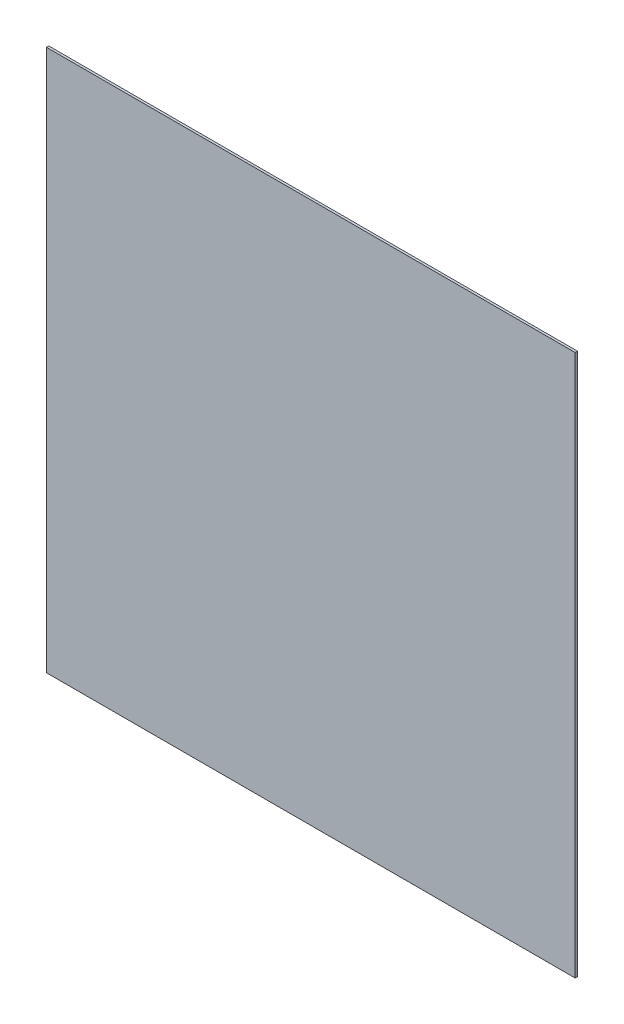
SolidWorks part; units mm, degrees
material "AISI 304"
ref_plane "Front Plane" through (0, 0, 0) normal (0, 0, 1) x (1, 0, 0)
ref_plane "Top Plane" through (0, 0, 0) normal (0, 1, 0) x (1, 0, 0)
ref_plane "Right Plane" through (0, 0, 0) normal (1, 0, 0) x (0, 0, -1)
sketch "Sketch1" plane through (0, 0, 0) normal (0, 0, 1) x (1, 0, 0)
  line L1 (-170.25, -174.5) -> (170.25, -174.5)
  line L2 (-170.25, -174.5) -> (-170.25, 174.5)
  line L3 (-170.25, 174.5) -> (170.25, 174.5)
  line L4 (170.25, -174.5) -> (170.25, 174.5)
  line L5 (-170.25, -174.5) -> (170.25, 174.5) construction
  line L6 (-170.25, 174.5) -> (170.25, -174.5) construction
  point P0 (0, 0)
  dimension "D1" = 340.5
  dimension "D2" = 349
base flange "Base-Flange1" sketch "Sketch1" thickness 1.5 reverse thickness direction no parameters "D1"=2
sketch "Bend-Lines1" [suppressed] plane through (0, 0, 0) normal (0, 1, 0) x (1, 0, 0)
sketch "Bounding-Box1" [suppressed] plane through (0, 0, 0) normal (0, 1, 0) x (1, 0, 0)
sheet metal parameters "Sheet-Metal1" thickness 1.5 parameters "D1"=2
flat pattern "Flat-Pattern1" [suppressed]
sketch "Bend-Lines2" plane through (0, 0, 0) normal (0, 1, 0) x (1, 0, 0)
sketch3d "Bounding-Box2" [suppressed]
  line L0 (170.25, 174.5, 0) -> (170.25, -174.5, 0) construction
  line L1 (-170.25, 174.5, 0) -> (-170.25, -174.5, 0) construction
  line L2 (170.25, 174.5, 0) -> (-170.25, 174.5, 0) construction
  line L3 (170.25, -174.5, 0) -> (-170.25, -174.5, 0) construction
